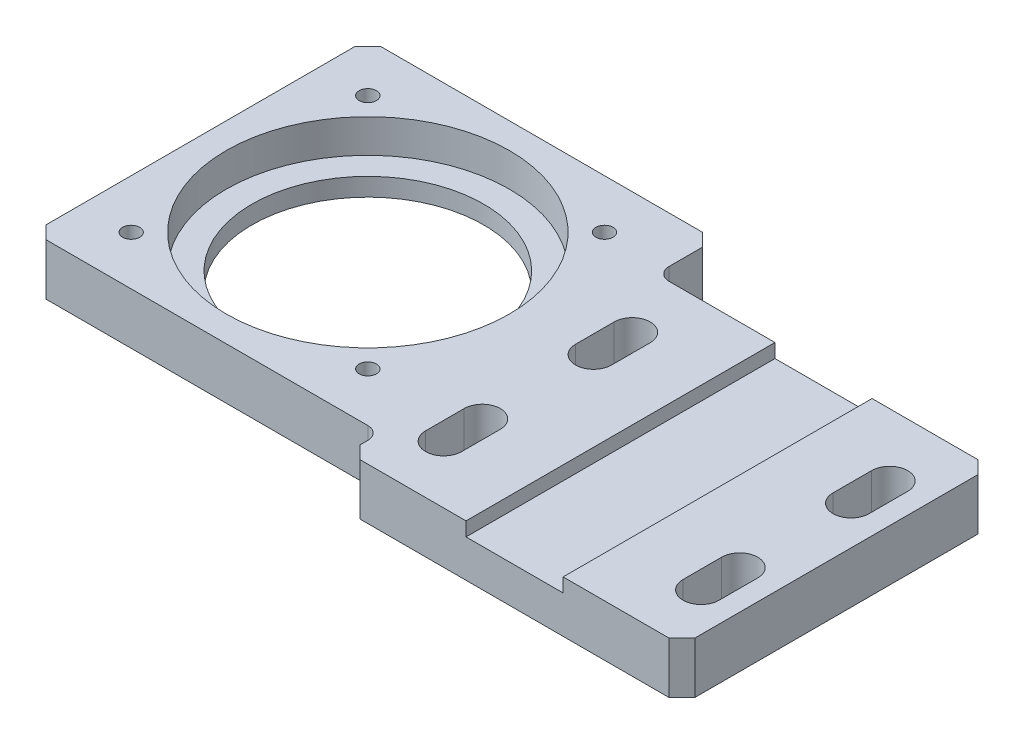
SolidWorks part; units mm, degrees
ref_plane "前视基准面" through (0, 0, 0) normal (0, 0, 1) x (1, 0, 0)
ref_plane "上视基准面" through (0, 0, 0) normal (0, 1, 0) x (1, 0, 0)
ref_plane "右视基准面" through (0, 0, 0) normal (1, 0, 0) x (0, 0, -1)
sketch "草图2" plane through (0, 0, 0) normal (0, 1, 0) x (1, 0, 0)
  line L0 (0, 0) -> (135, 0)
  line L1 (135, 0) -> (135, -23)
  line L2 (135, -23) -> (265, -23)
  line L3 (265, -23) -> (265, -143)
  line L4 (265, -143) -> (135, -143)
  line L5 (135, -143) -> (135, -130)
  line L6 (135, -130) -> (0, -130)
  line L7 (0, -130) -> (0, 0)
  point P9 (200, -143)
  dimension "D1" = 130
  dimension "D2" = 120
  dimension "D3" = 143
  dimension "D4" = 135
  dimension "D5" = 130
extrude "凸台-拉伸1" add sketch "草图2" along normal blind 20
sketch "草图3" plane through (0, 20, 0) normal (0, 1, 0) x (1, 0, 0)
  line L0 (0, 0) -> (0, -130) construction
  circle A0 centre (65, -65) radius 45
  point P5 (0, -65)
  dimension "D1" = 90
  dimension "D2" = 65
extrude "切除-拉伸1" cut sketch "草图3" against normal through all
sketch "草图4" plane through (0, 20, 0) normal (0, 1, 0) x (1, 0, 0)
  circle A0 centre (65, -65) radius 55
  dimension "D1" = 110
extrude "切除-拉伸2" cut sketch "草图4" against normal blind 13
sketch "草图5" plane through (0, 20, 0) normal (0, 1, 0) x (1, 0, 0)
  line L0 (181.1483, -23) -> (181.1483, -143)
  line L1 (265, -23) -> (135, -23) construction
  line L2 (135, -143) -> (265, -143) construction
  line L3 (218.8517, -23) -> (218.8517, -143)
  line L4 (200, -23) -> (200, -143) construction
  line L5 (265, -143) -> (265, -23) construction
  line L6 (181.1483, -23) -> (218.8517, -23)
  line L7 (218.8517, -143) -> (181.1483, -143)
  dimension "D1" = 65
extrude "切除-拉伸3" cut sketch "草图5" against normal blind 5.4
sketch "草图6" plane through (0, 20, 0) normal (0, 1, 0) x (1, 0, 0)
  line L0 (265, -83) -> (145.3453, -83) construction
  line L1 (265, -143) -> (265, -23) construction
  line L2 (200, -23) -> (200, -143) construction
  line L3 (218.8517, -23) -> (181.1483, -23) construction
  line L4 (181.1483, -143) -> (218.8517, -143) construction
  line L5 (150, -47.3125) -> (150, -62.3125) construction
  line L6 (157, -47.3125) -> (157, -62.3125)
  line L7 (143, -47.3125) -> (143, -62.3125)
  line L8 (150, -105.5582) -> (150, -120.5582) construction
  line L9 (157, -105.5582) -> (157, -120.5582)
  line L10 (143, -105.5582) -> (143, -120.5582)
  line L11 (250, -47.3125) -> (250, -62.3125) construction
  line L12 (257, -47.3125) -> (257, -62.3125)
  line L13 (243, -47.3125) -> (243, -62.3125)
  line L14 (250, -105.5582) -> (250, -120.5582) construction
  line L15 (257, -105.5582) -> (257, -120.5582)
  line L16 (243, -105.5582) -> (243, -120.5582)
  arc A0 (157, -47.3125) -> (143, -47.3125) centre (150, -47.3125) ccw
  arc A1 (143, -62.3125) -> (157, -62.3125) centre (150, -62.3125) ccw
  arc A2 (157, -105.5582) -> (143, -105.5582) centre (150, -105.5582) ccw
  arc A3 (143, -120.5582) -> (157, -120.5582) centre (150, -120.5582) ccw
  arc A4 (257, -47.3125) -> (243, -47.3125) centre (250, -47.3125) ccw
  arc A5 (243, -62.3125) -> (257, -62.3125) centre (250, -62.3125) ccw
  arc A6 (257, -105.5582) -> (243, -105.5582) centre (250, -105.5582) ccw
  arc A7 (243, -120.5582) -> (257, -120.5582) centre (250, -120.5582) ccw
  point P12 (150, -54.8125)
  point P17 (150, -113.0582)
  point P24 (250, -54.8125)
  point P31 (250, -113.0582)
  dimension "D2" = 29
  dimension "D1" = 14
  dimension "D3" = 100
extrude "切除-拉伸4" cut sketch "草图6" against normal through all
fillet "圆角1" radius 5 2 edges at (135, 10, 23) (135, 10, 130)
chamfer "倒角1" distance 5 6 edges at (265, 10, 23) (265, 10, 143) (135, 10, 143) (135, 10, 0) (0, 10, 130) (0, 10, 0)
sketch "草图7" plane through (0, 20, 0) normal (0, 1, 0) x (1, 0, 0)
  line L0 (65, -65) -> (65, 25.1133) construction
  line L1 (65, -65) -> (110.9619, -19.0381) construction
  circle A1 centre (65, -65) radius 65 construction
  circle A2 centre (110.9619, -19.0381) radius 3.35
  circle A3 centre (110.9619, -110.9619) radius 3.35
  circle A4 centre (19.0381, -110.9619) radius 3.35
  circle A5 centre (19.0381, -19.0381) radius 3.35
  point P4 (0, 0)
  point P15 (65, -65)
  dimension "D1" = 130
  dimension "D2" = 6.7
  dimension "D3" = 45
  dimension "D4" = 4
extrude "切除-拉伸5" cut sketch "草图7" against normal through all
